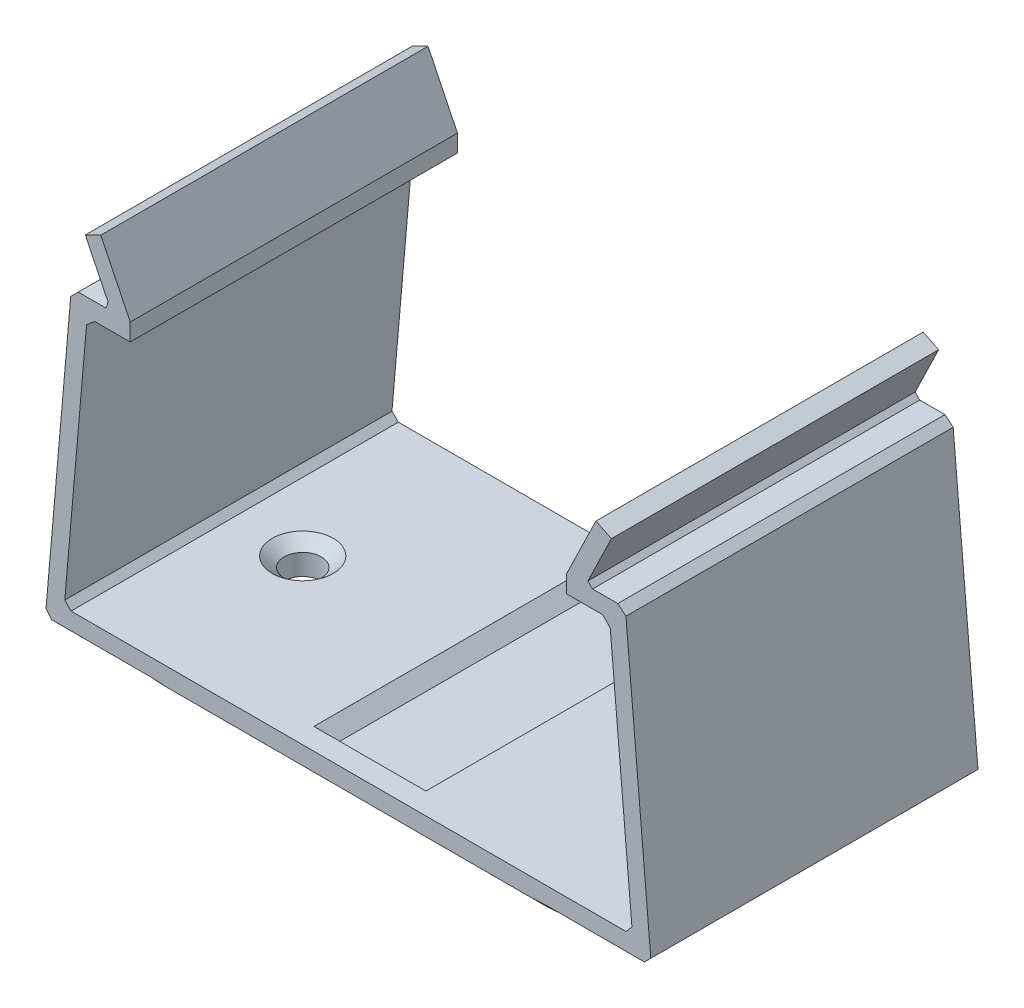
SolidWorks part; units mm, degrees
ref_plane "Front Plane" through (0, 0, 0) normal (0, 0, 1) x (1, 0, 0)
ref_plane "Top Plane" through (0, 0, 0) normal (0, 1, 0) x (1, 0, 0)
ref_plane "Right Plane" through (0, 0, 0) normal (1, 0, 0) x (0, 0, -1)
sketch "Sketch1" plane through (0, 0, 0) normal (0, 0, 1) x (1, 0, 0)
  line L0 (0, 0) -> (0, 24) construction
  line L1 (-32.1643, 32.5) -> (-27.5552, 32.5)
  line L2 (-30.3316, 30.5) -> (-33, 0)
  line L3 (-33, 0) -> (0, 0)
  line L4 (-32.1643, 32.5) -> (-35.1826, -2)
  line L5 (-35.1826, -2) -> (0, -2)
  line L6 (-30.3316, 30.5) -> (-25.3316, 30.5)
  line L7 (-25.3316, 32.5) -> (-25.3316, 30.5)
  line L8 (35.1826, -2) -> (0, -2)
  line L9 (33, 0) -> (0, 0)
  line L10 (25.3316, 32.5) -> (25.3316, 30.5)
  line L11 (30.3316, 30.5) -> (25.3316, 30.5)
  line L12 (32.1643, 32.5) -> (35.1826, -2)
  line L13 (30.3316, 30.5) -> (33, 0)
  line L14 (32.1643, 32.5) -> (27.5552, 32.5)
  line L15 (-25.3316, 32.5) -> (-28.7479, 39.5303)
  line L16 (-27.5552, 32.5) -> (-30.5468, 38.6562)
  line L17 (-28.7479, 39.5303) -> (-30.5468, 38.6562)
  line L18 (-27.1305, 31.6259) -> (-30.5468, 38.6562) construction
  line L19 (-32.1643, 32.5) -> (-25.3316, 32.5) construction
  line L20 (28.7479, 39.5303) -> (30.5468, 38.6562)
  line L21 (27.5552, 32.5) -> (30.5468, 38.6562)
  line L22 (25.3316, 32.5) -> (28.7479, 39.5303)
  dimension "D1" = 85
  dimension "D2" = 30.5
  dimension "D3" = 33
  dimension "D4" = 2
  dimension "D5" = 5
  dimension "D6" = 2
extrude "Boss-Extrude1" add sketch "Sketch1" along normal blind 38
sketch "Sketch5" plane through (0, -2, 0) normal (0, -1, 0) x (1, 0, 0)
  line L0 (-31.5, 0) -> (-31.5, 38)
  line L1 (-35.1826, 38) -> (35.1826, 38) construction
  line L3 (-31.5, 38) -> (31.5, 38)
  line L4 (-31.5, 0) -> (31.5, 0)
  line L5 (0, 0) -> (0, 50) construction
  line L6 (24.3, 15) -> (-24.3, 15) construction
  line L7 (31.5, 0) -> (31.5, 38)
  dimension "D1" = 48.6
  dimension "D2" = 63
extrude "Boss-Extrude2" add sketch "Sketch5" along normal blind 1.6
sketch "Sketch9" plane through (0, 0, 0) normal (0, 1, 0) x (1, 0, 0)
  line L1 (-5, -34) -> (-5, -4)
  line L2 (-5, -34) -> (5, -34)
  line L3 (5, -34) -> (5, -4)
  line L4 (-5, -4) -> (5, -4)
  line L5 (-5, -34) -> (5, -4) construction
  line L6 (5, -34) -> (-5, -4) construction
  point P0 (0, -19)
  dimension "D1" = 10
  dimension "D3" = 30
extrude "Cut-Extrude4" cut sketch "Sketch9" against normal blind 1.5
chamfer "Chamfer4" distance 1.5 angle 45 4 edges at (0, 0, 34) (-5, 0, 19) (0, 0, 4) (5, 0, 19)
chamfer "Chamfer6" distance 0.8 angle 45 4 edges at (-35.1826, -2, 19) (35.1826, -2, 19) (33, 0, 19) (-33, 0, 19)
chamfer "Chamfer7" distance 0.8 angle 45 6 edges at (-30.3316, 30.5, 19) (30.3316, 30.5, 19) (32.1643, 32.5, 19) (-32.1643, 32.5, 19) (27.5552, 32.5, 19) (-27.5552, 32.5, 19)
sketch "Sketch12" plane through (0, 0, 0) normal (0, 1, 0) x (1, 0, 0)
  line L0 (24.3, -19) -> (-24.3, -19) construction
  dimension "D1" = 48.6
hole_wizard "CSK for #6 Flat Head Machine Screw (100)1" positions "Sketch13" profile "Sketch14" countersink size "#6" standard "ANSI Inch"
sketch "Sketch13" plane through (0, 0, 0) normal (0, 1, 0) x (1, 0, 0)
  point P0 (24.3, -19)
  point P3 (-24.3, -19)
sketch "Sketch14" plane through (24.3, 0, 19) normal (1, 0, 0) x (0, 0, 1)
  line L0 (0, 0) -> (0, 3.6)
  line L1 (0, 3.6) -> (2.1526, 3.6)
  line L2 (2.1526, 3.6) -> (2.1526, 1.1669)
  line L3 (2.1526, 1.1669) -> (3.5433, 0)
  line L5 (3.5433, 0) -> (0, 0)
  line L6 (-2.1526, 1.1669) -> (-3.5433, 0) construction
  line L11 (0, -6.35) -> (0, 107.95) construction
  dimension "Thru Hole Dia." = 4.3053
  dimension "Thru Hole Depth" = 3.6
  dimension "Near C'Sink Dia." = 7.0866
  dimension "Near C'Sink Angle" = 100
fillet "Fillet1" radius 10 4 edges at (-31.5, -2.8, 38) (-31.5, -2.8, 0) (31.5, -2.8, 0) (31.5, -2.8, 38)
chamfer "Chamfer10" distance 1.5 angle 45 8 edges at (31.5, -3.6, 19) (28.5711, -3.6, 35.0711) (28.5711, -3.6, 2.9289) (0, -3.6, 38) (0, -3.6, 0) (-28.5711, -3.6, 35.0711) (-28.5711, -3.6, 2.9289) (-31.5, -3.6, 19)
